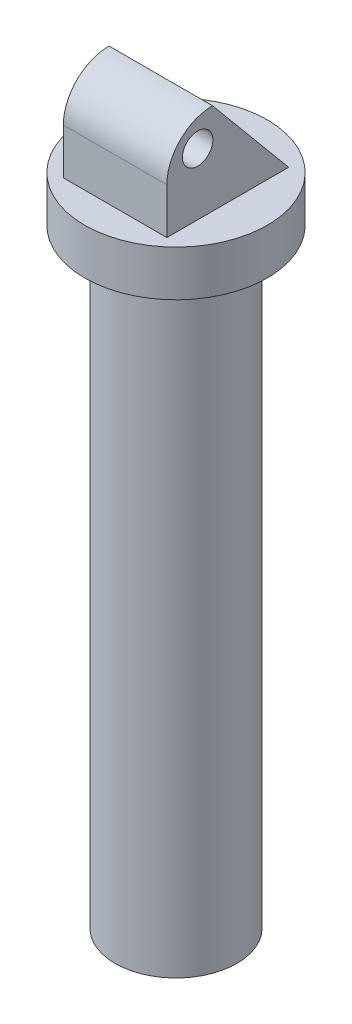
SolidWorks part; units mm, degrees
ref_plane "Front Plane" through (0, 0, 0) normal (0, 0, 1) x (1, 0, 0)
ref_plane "Top Plane" through (0, 0, 0) normal (0, 1, 0) x (1, 0, 0)
ref_plane "Right Plane" through (0, 0, 0) normal (1, 0, 0) x (0, 0, -1)
sketch "Sketch1" plane through (0, 0, 0) normal (0, 1, 0) x (1, 0, 0)
  circle A0 centre (0, 0) radius 20
  dimension "D1" = 40
extrude "Boss-Extrude1" add sketch "Sketch1" along normal blind 200
sketch "Sketch2" plane through (0, 200, 0) normal (0, 1, 0) x (1, 0, 0)
  circle A0 centre (0, 0) radius 30
  dimension "D1" = 60
extrude "Boss-Extrude2" add sketch "Sketch2" along normal blind 15
sketch "Sketch3" plane through (0, 215, 0) normal (0, 1, 0) x (1, 0, 0)
  line L1 (-17, -20) -> (17, -20)
  line L2 (-17, -20) -> (-17, 20)
  line L3 (-17, 20) -> (17, 20)
  line L4 (17, -20) -> (17, 20)
  line L5 (-17, -20) -> (17, 20) construction
  line L6 (-17, 20) -> (17, -20) construction
  point P0 (0, 0)
  dimension "D1" = 40
  dimension "D2" = 34
extrude "Boss-Extrude3" add sketch "Sketch3" along normal blind 30
sketch "Sketch4" plane through (17, 0, 0) normal (1, 0, 0) x (0, 0, -1)
  line L0 (20, 215) -> (-5, 245)
  line L1 (-20, 245) -> (20, 245) construction
  line L2 (-20, 245) -> (-20, 215) construction
  line L3 (-5, 245) -> (20, 245)
  line L4 (20, 245) -> (20, 215)
  dimension "D1" = 15
extrude "Cut-Extrude1" cut sketch "Sketch4" against normal blind 59
fillet "Fillet1" radius 15 1 edges at (0, 245, 20)
sketch "Sketch5" plane through (17, 0, 0) normal (1, 0, 0) x (0, 0, -1)
  line L0 (-5.3089, 229.7502) -> (-14.9117, 241.2735) construction
  line L1 (-5, 245) -> (20, 215) construction
  circle A1 centre (-9.8919, 235.2498) radius 5
  dimension "D2" = 10
  dimension "D1" = 10
extrude "Cut-Extrude2" cut sketch "Sketch5" against normal blind 59
